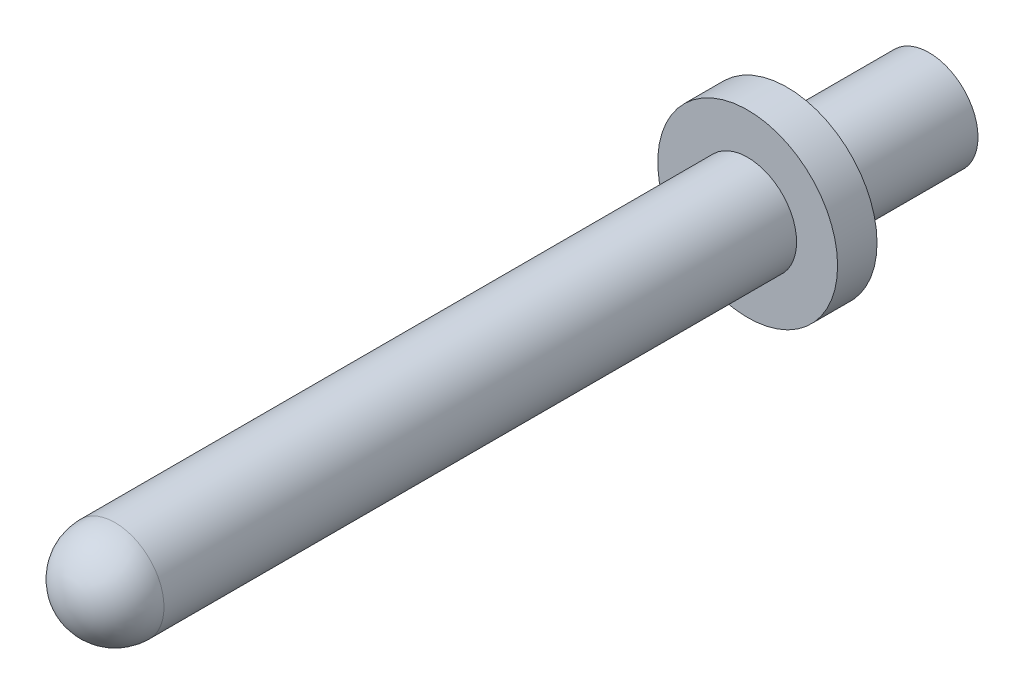
SolidWorks part; units mm, degrees
ref_plane "Front Plane" through (0, 0, 0) normal (0, 0, 1) x (1, 0, 0)
ref_plane "Top Plane" through (0, 0, 0) normal (0, 1, 0) x (1, 0, 0)
ref_plane "Right Plane" through (0, 0, 0) normal (1, 0, 0) x (0, 0, -1)
sketch "Sketch1" plane through (0, 0, 0) normal (0, 1, 0) x (1, 0, 0)
  line L0 (0.5461, 11.6078) -> (0, 11.2903)
  line L1 (0, 0) -> (0.7874, 0)
  line L2 (0, 0) -> (0, 10.9728)
  line L3 (0, 10.9728) -> (0.7874, 10.9728)
  line L4 (0.7874, 0) -> (0.7874, 10.9728)
  line L5 (0, 10.9728) -> (1.4478, 10.9728)
  line L6 (0, 10.9728) -> (0, 11.6078)
  line L7 (0, 11.6078) -> (1.4478, 11.6078)
  line L8 (1.4478, 10.9728) -> (1.4478, 11.6078)
  line L9 (0.5461, 11.6078) -> (0.7874, 11.6078)
  line L10 (0.5461, 11.6078) -> (0.5461, 13.8938)
  line L11 (0.5461, 13.8938) -> (0.7874, 13.8938)
  line L12 (0.7874, 11.6078) -> (0.7874, 13.8938)
  circle A0 centre (0, 0.7874) radius 0.7874
  dimension "D1" = 10.9728
  dimension "D2" = 0.7874
  dimension "D3" = 0.635
  dimension "D4" = 0.5461
  dimension "D5" = 0.7874
  dimension "D6" = 2.286
  dimension "D7" = 1.4478
  dimension "D8" = 0.3175
revolve "Revolve1" add sketch "Sketch1" angle 360 about L2 region at (0.7803, 0, -11.2683) region at (0.6668, 0, -12.7508) region at (0.3975, 0, -6.1877) region at (0.3342, 0, -0.7874)
